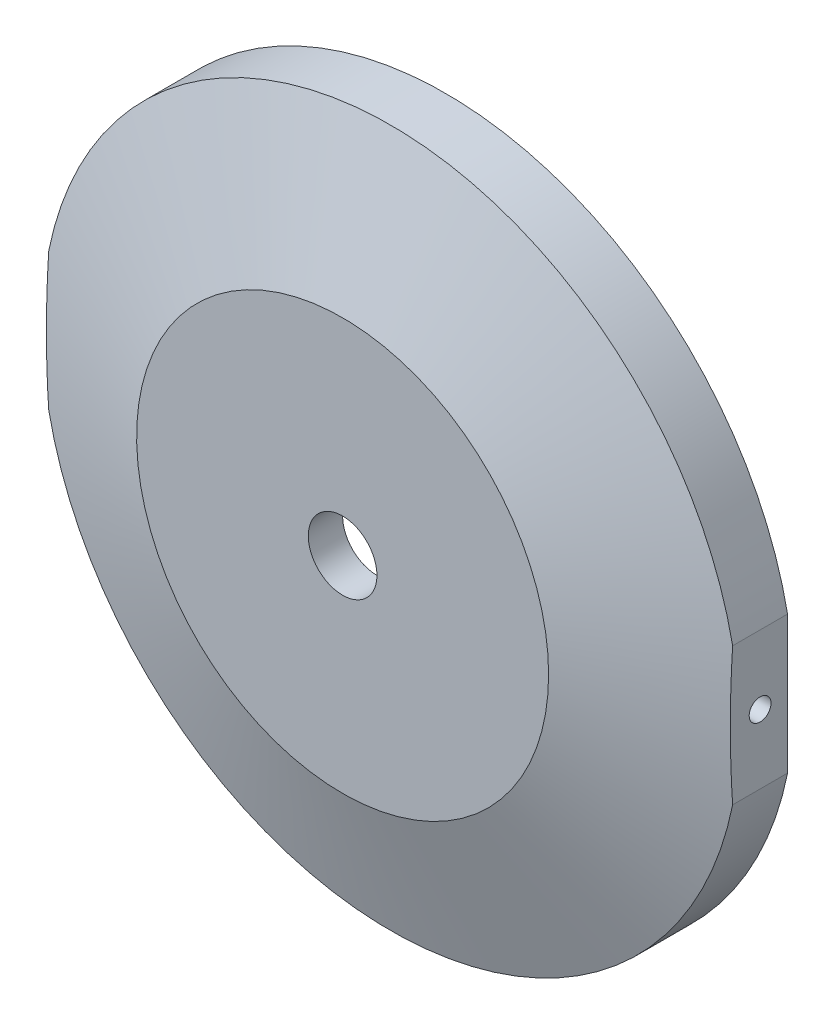
SolidWorks part; units mm, degrees
material "1060 Alloy"
ref_plane "Front Plane" through (0, 0, 0) normal (0, 0, 1) x (1, 0, 0)
ref_plane "Top Plane" through (0, 0, 0) normal (0, 1, 0) x (1, 0, 0)
ref_plane "Right Plane" through (0, 0, 0) normal (1, 0, 0) x (0, 0, -1)
sketch "Sketch2" plane through (0, 0, 0) normal (1, 0, 0) x (0, 0, -1)
  line L0 (0, 0) -> (0, 5) construction
  line L1 (0, 5) -> (5, 5)
  line L2 (5, 5) -> (5, 30)
  line L3 (5, 30) -> (15, 40.8)
  line L4 (15, 40.8) -> (15, 50.8)
  line L5 (15, 50.8) -> (7, 50.8)
  line L8 (0, 30) -> (0, 5)
  line L9 (0, 30) -> (7, 50.8)
  line L10 (-1000, 0) -> (49000, 0) construction
  dimension "D1" = 5
  dimension "D2" = 5
  dimension "D3" = 50.8
  dimension "D4" = 25
  dimension "D5" = 8
  dimension "D6" = 10
  dimension "D7" = 15
revolve "Revolve1" add sketch "Sketch2" angle 360 about L10 region at (0, 31.5423, -5.9724)
ref_plane "Plane1" through (50.8, 0, 0) normal (1, 0, 0) x (0, 0, -1)
sketch "Sketch5" plane through (50.8, 0, 0) normal (1, 0, 0) x (0, 0, -1)
  line L3 (22.5, -12.5) -> (-2.5, -12.5)
  line L4 (22.5, -12.5) -> (22.5, 12.5)
  line L5 (22.5, 12.5) -> (-2.5, 12.5)
  line L6 (-2.5, -12.5) -> (-2.5, 12.5)
  line L7 (22.5, -12.5) -> (-2.5, 12.5) construction
  line L8 (22.5, 12.5) -> (-2.5, -12.5) construction
  point P0 (10, 0)
  dimension "D1" = 10
  dimension "D2" = 25
extrude "Cut-Extrude3" cut sketch "Sketch5" against normal blind 1 contours L4 L3 L6 L5
sketch "Sketch6" plane through (49.8, 0, 0) normal (1, 0, 0) x (0, 0, -1)
  line L0 (7, 0) -> (15, 0) construction
  point P2 (0, 0)
  point P6 (11, 0)
  dimension "D1" = 8
hole_wizard "1/8 (0.125) Diameter Hole2" positions "3DSketch3" profile "Sketch7" hole size "1/8" standard "ANSI Inch" end condition up to next
sketch3d "3DSketch3"
  point P0 (49.8, 0, -11)
sketch "Sketch7" plane through (49.8, 0, -11) normal (0, 1, 0) x (0, 0, -1)
  line L0 (0, 0) -> (0, 13.32)
  line L1 (0, 13.32) -> (1.5875, 13.32)
  line L2 (1.5875, 13.32) -> (1.5875, 0)
  line L5 (1.5875, 0) -> (0, 0)
  line L11 (0, -6.35) -> (0, 107.95) construction
  dimension "Thru Hole Dia." = 3.175
  dimension "Thru Hole Depth" = 13.32
mirror "Mirror2" about plane through (0, 0, 0) normal (1, 0, 0) of "1/8 (0.125) Diameter Hole2", "Cut-Extrude3"
fillet "Fillet1" [suppressed] radius 4
fillet "Fillet2" [suppressed] radius 4
